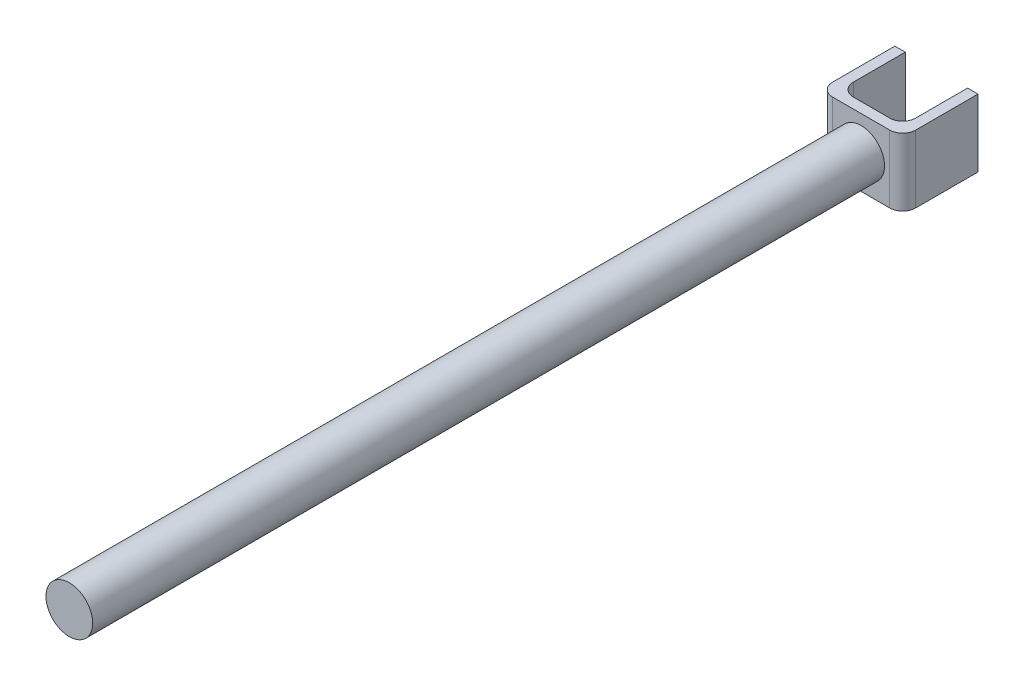
SolidWorks part; units mm, degrees
ref_plane "Front Plane" through (0, 0, 0) normal (0, 0, 1) x (1, 0, 0)
ref_plane "Top Plane" through (0, 0, 0) normal (0, 1, 0) x (1, 0, 0)
ref_plane "Right Plane" through (0, 0, 0) normal (1, 0, 0) x (0, 0, -1)
sketch "Sketch1" plane through (0, 0, 0) normal (0, 1, 0) x (1, 0, 0)
  line L0 (0, 0) -> (0, -20.7763) construction
  line L1 (7, -20.7763) -> (-7, -20.7763)
  line L2 (12, -15.7763) -> (12, 4.2237)
  line L3 (12, 4.2237) -> (16, 4.2237)
  line L4 (16, 4.2237) -> (16, -19.7763)
  line L5 (11, -24.7763) -> (-11, -24.7763)
  line L6 (-16, 4.2237) -> (-16, -19.7763)
  line L7 (-12, 4.2237) -> (-16, 4.2237)
  line L8 (-12, -15.7763) -> (-12, 4.2237)
  arc A0 (16, -19.7763) -> (11, -24.7763) centre (11, -19.7763) cw
  arc A1 (7, -20.7763) -> (12, -15.7763) centre (7, -15.7763) ccw
  arc A2 (-7, -20.7763) -> (-12, -15.7763) centre (-7, -15.7763) cw
  arc A3 (-16, -19.7763) -> (-11, -24.7763) centre (-11, -19.7763) ccw
  point P6 (0, -20.7763)
  point P13 (12, -20.7763)
  point P20 (0, -24.7763)
  point P22 (-12, -20.7763)
  dimension "D5" = 5
  dimension "D1" = 4
  dimension "D2" = 4
  dimension "D3" = 25
  dimension "D4" = 12
extrude "Boss-Extrude1" add sketch "Sketch1" along normal blind 13 and the other way blind 13
sketch "Sketch2" plane through (0, 0, 24.7763) normal (0, 0, 1) x (1, 0, 0)
  circle A0 centre (0, 0) radius 9
  dimension "D1" = 18
extrude "Boss-Extrude2" add sketch "Sketch2" along normal blind 305
sketch "Sketch3" plane through (0, 0, 0) normal (0, 1, 0) x (1, 0, 0)
  line L0 (0, 0) -> (0, -400) construction
  point P4 (0, -400)
  point P5 (0, 0)
  dimension "D1" = 400
